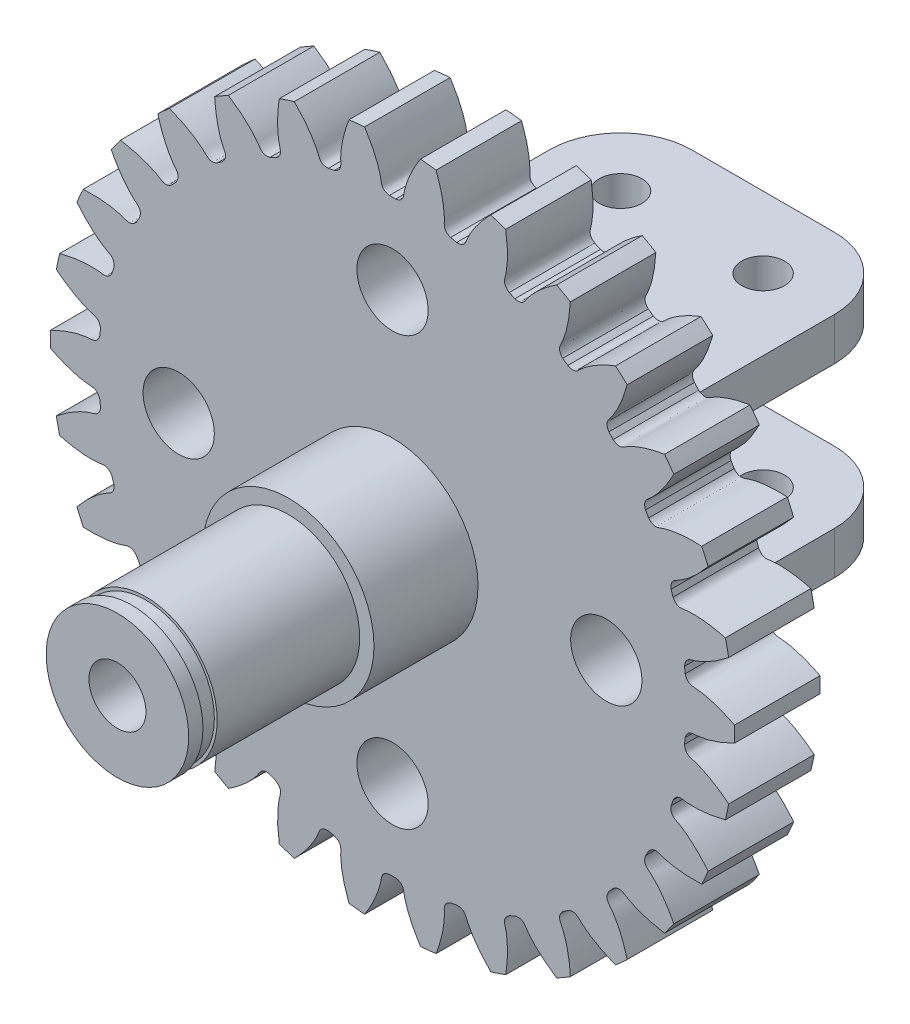
SolidWorks part; units mm, degrees
material "1060 合金"
ref_plane "前视基准面" through (0, 0, 0) normal (0, 0, 1) x (1, 0, 0)
ref_plane "上视基准面" through (0, 0, 0) normal (0, 1, 0) x (1, 0, 0)
ref_plane "右视基准面" through (0, 0, 0) normal (1, 0, 0) x (0, 0, -1)
sketch "草图1" plane through (0, 0, 0) normal (0, 0, 1) x (1, 0, 0)
  circle A0 centre (0, 0) radius 24
extrude "凸台-拉伸1" add sketch "草图1" along normal blind 6
ref_axis "基准轴1" through (0, 0, 6) along (0, 0, -1)
sketch "草图2" plane through (0, 0, 0) normal (0, 0, 1) x (1, 0, 0)
  line L0 (0, 0) -> (0, 24) construction
  circle A0 centre (0, 0) radius 24 construction
  arc A1 (0.2183, 20.6238) -> (-0.2183, 20.6238) centre (0, 0) ccw
  arc A2 (5.0495, 27.2858) -> (-5.0495, 27.2858) centre (0, 0) ccw
  spline S0 degree 3 poles (0.2183, 20.6238) (0.7623, 20.7195) (0.7655, 21.0707) (0.8385, 21.4329) (0.8549, 21.5072) (0.8749, 21.5894) (0.8986, 21.6793) (0.9264, 21.7769) (0.9587, 21.8821) (0.9957, 21.9945) (1.0378, 22.1142) (1.0852, 22.241) (1.1382, 22.3746) (1.1972, 22.515) (1.2624, 22.6619) (1.3341, 22.8151) (1.4126, 22.9744) (1.4981, 23.1396) (1.591, 23.3106) (1.6914, 23.487) (1.7997, 23.6686) (1.9161, 23.8552) (2.0408, 24.0465) (2.1741, 24.2422) (2.3161, 24.4422) (2.4671, 24.6461) (2.6274, 24.8536) (2.7971, 25.0644) (2.9764, 25.2783) (3.1655, 25.4949) (3.3646, 25.714) (3.5738, 25.9352) (3.7934, 26.1582) (4.0234, 26.3827) (4.264, 26.6083) (4.6034, 26.9139) (4.868, 27.1381) (5.0495, 27.2858) knots 0 0 0 0 0.115324 0.123413 0.132512 0.142623 0.153745 0.165878 0.179022 0.193177 0.208343 0.22452 0.241708 0.259907 0.279117 0.299338 0.320571 0.342814 0.366068 0.390334 0.41561 0.441898 0.469196 0.497506 0.526827 0.557158 0.588501 0.620855 0.65422 0.688595 0.723982 0.76038 0.797789 0.836209 0.87564 0.916083 1 1 1 1
  spline S1 degree 3 poles (-0.2183, 20.6238) (-0.7623, 20.7195) (-0.7655, 21.0707) (-0.8385, 21.4329) (-0.8549, 21.5072) (-0.8749, 21.5894) (-0.8986, 21.6793) (-0.9264, 21.7769) (-0.9587, 21.8821) (-0.9957, 21.9945) (-1.0378, 22.1142) (-1.0852, 22.241) (-1.1382, 22.3746) (-1.1972, 22.515) (-1.2624, 22.6619) (-1.3341, 22.8151) (-1.4126, 22.9744) (-1.4981, 23.1396) (-1.591, 23.3106) (-1.6914, 23.487) (-1.7997, 23.6686) (-1.9161, 23.8552) (-2.0408, 24.0465) (-2.1741, 24.2422) (-2.3161, 24.4422) (-2.4671, 24.6461) (-2.6274, 24.8536) (-2.7971, 25.0644) (-2.9764, 25.2783) (-3.1655, 25.4949) (-3.3646, 25.714) (-3.5738, 25.9352) (-3.7934, 26.1582) (-4.0234, 26.3827) (-4.264, 26.6083) (-4.6034, 26.9139) (-4.868, 27.1381) (-5.0495, 27.2858) knots 0 0 0 0 0.115324 0.123413 0.132512 0.142623 0.153745 0.165878 0.179022 0.193177 0.208343 0.22452 0.241708 0.259907 0.279117 0.299338 0.320571 0.342814 0.366068 0.390334 0.41561 0.441898 0.469196 0.497506 0.526827 0.557158 0.588501 0.620855 0.65422 0.688595 0.723982 0.76038 0.797789 0.836209 0.87564 0.916083 1 1 1 1
extrude "切除-拉伸1" cut sketch "草图2" along normal through all
pattern_circular "阵列(圆周)1" count 30 every 12 about axis through (0, 0, 6) along (0, 0, -1) of "切除-拉伸1"
sketch "草图3" plane through (0, 0, 0) normal (0, 0, 1) x (1, 0, 0)
  circle A0 centre (0, 0) radius 22.5 construction
  dimension "Dn" = 45
sketch "草图4" plane through (0, 0, 6) normal (0, 0, 1) x (1, 0, 0)
  circle A0 centre (0, 0) radius 6
  dimension "D1" = 12
extrude "凸台-拉伸2" add sketch "草图4" along normal blind 7.3
sketch "草图5" plane through (0, 0, 13.3) normal (0, 0, 1) x (1, 0, 0)
  circle A0 centre (0, 0) radius 5
  dimension "D1" = 10
extrude "凸台-拉伸3" add sketch "草图5" along normal blind 12
sketch "草图6" plane through (0, 0, 0) normal (0, 0, -1) x (-1, 0, 0)
  line L0 (-10, 5) -> (10, 5)
  line L1 (-10, 8) -> (10, 8)
  line L2 (-10, 8) -> (-10, -8)
  line L3 (-10, -8) -> (10, -8)
  line L4 (10, 8) -> (10, -8)
  line L5 (-10, 8) -> (10, -8) construction
  line L6 (-10, -8) -> (10, 8) construction
  line L7 (-10, -5) -> (10, -5)
  point P0 (0, 0)
  dimension "D1" = 16
  dimension "D2" = 20
  dimension "D3" = 3
  dimension "D4" = 3
extrude "凸台-拉伸4" add sketch "草图6" along normal blind 20 contours L4 L1 L2 L0 | L7 L2 L3 L4 region at (0, 6.5, 0) region at (0, -6.5, 0)
sketch "草图7" plane through (0, 8, 0) normal (0, 1, 0) x (1, 0, 0)
  line L0 (10, 20) -> (-10, 20) construction
  line L1 (-5, 15) -> (5, 15) construction
  line L2 (-5, 15) -> (-5, 5) construction
  line L3 (-5, 5) -> (5, 5) construction
  line L4 (5, 15) -> (5, 5) construction
  line L5 (-5, 15) -> (5, 5) construction
  line L6 (-5, 5) -> (5, 15) construction
  line L7 (10, 20) -> (10, 0) construction
  circle A0 centre (5, 15) radius 1.5
  circle A1 centre (5, 5) radius 1.5
  circle A2 centre (-5, 5) radius 1.5
  circle A3 centre (-5, 15) radius 1.5
  point P0 (0, 10)
  dimension "D4" = 3
  dimension "D5" = 3
  dimension "D6" = 3
  dimension "D7" = 3
  dimension "D1" = 10
  dimension "D2" = 5
  dimension "D3" = 5
extrude "切除-拉伸2" cut sketch "草图7" against normal blind 20
fillet "圆角1" radius 5 4 edges at (-10, -6.5, -20) (-10, 6.5, -20) (10, 6.5, -20) (10, -6.5, -20)
ref_plane "基准面1" through (0, 0, 24.3) normal (0, 0, 1) x (1, 0, 0)
sketch "草图8" plane through (0, 0, 24.3) normal (0, 0, 1) x (1, 0, 0)
  circle A0 centre (0, 0) radius 5
  circle A1 centre (0, 0) radius 4.8
  dimension "D1" = 10
  dimension "D2" = 9.6
extrude "切除-拉伸3" cut sketch "草图8" against normal blind 1
sketch "草图9" plane through (0, 0, 25.3) normal (0, 0, 1) x (1, 0, 0)
  circle A0 centre (0, 0) radius 2
  dimension "D1" = 4
extrude "切除-拉伸4" cut sketch "草图9" against normal through all
sketch "草图10" plane through (0, 0, 6) normal (0, 0, 1) x (1, 0, 0)
  circle A0 centre (0, 0) radius 15 construction
  circle A1 centre (0, 15) radius 2.5
  circle A2 centre (-15, 0) radius 2.5
  circle A3 centre (0, -15) radius 2.5
  circle A4 centre (15, 0) radius 2.5
  dimension "D1" = 30
  dimension "D2" = 5
  dimension "D3" = 5
  dimension "D4" = 5
  dimension "D5" = 5
extrude "切除-拉伸5" cut sketch "草图10" against normal blind 11
